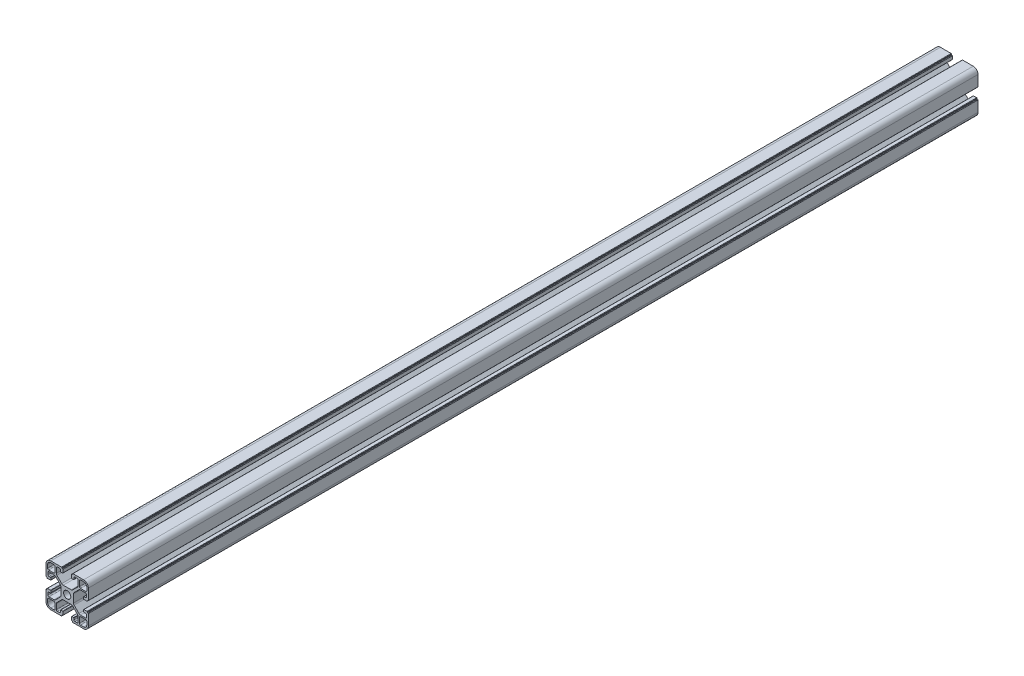
SolidWorks part; units mm, degrees
note: '?' marks a value the reader was unsure of.
material "6063-T5"
ref_plane "前视基准面" through (0, 0, 0) normal (0, 0, 1) x (1, 0, 0)
ref_plane "上视基准面" through (0, 0, 0) normal (0, 1, 0) x (1, 0, 0)
ref_plane "右视基准面" through (0, 0, 0) normal (1, 0, 0) x (0, 0, -1)
sketch "草图1" plane through (0, 0, 0) normal (0, 0, 1) x (1, 0, 0)
  line L0 (5.1, -19.2) -> (5.1, -19.7)
  line L1 (4.4, -19) -> (4.9, -19)
  line L2 (5.4, -20) -> (15.5, -20)
  line L3 (4.1, -15.8) -> (4.1, -18.8)
  line L4 (20, -15.5) -> (20, -5.4)
  line L5 (6.1, -15.5) -> (4.4, -15.5)
  line L6 (19.7, -5.1) -> (19.2, -5.1)
  line L7 (6.4, -17.2) -> (6.4, -15.8)
  line L8 (19, -4.9) -> (19, -4.4)
  line L9 (9.25, -18.2) -> (7.4, -18.2)
  line L10 (18.7, -4.1) -> (15.8, -4.1)
  line L11 (10.25, -12.4926) -> (10.25, -17.2)
  line L12 (15.5, -4.4) -> (15.5, -6.1)
  line L13 (5.1716, -6.5858) -> (9.6642, -11.0784)
  line L14 (15.8, -6.4) -> (17.2, -6.4)
  line L15 (-3.7574, -6) -> (3.7574, -6)
  line L16 (18.2, -7.4) -> (18.2, -9.25)
  line L17 (-9.6642, -11.0784) -> (-5.1716, -6.5858)
  line L18 (17.2, -10.25) -> (12.4926, -10.25)
  line L19 (-10.25, -17.2) -> (-10.25, -12.4926)
  line L20 (11.0784, -9.6642) -> (6.5858, -5.1716)
  line L21 (-7.4, -18.2) -> (-9.25, -18.2)
  line L22 (6, -3.7574) -> (6, 3.7574)
  line L23 (-6.4, -15.8) -> (-6.4, -17.2)
  line L24 (6.5858, 5.1716) -> (11.0784, 9.6642)
  line L25 (-4.4, -15.5) -> (-6.1, -15.5)
  line L26 (12.4926, 10.25) -> (17.2, 10.25)
  line L27 (-4.1, -18.8) -> (-4.1, -15.8)
  line L28 (18.2, 9.25) -> (18.2, 7.4)
  line L29 (-4.9, -19) -> (-4.4, -19)
  line L30 (17.2, 6.4) -> (15.8, 6.4)
  line L31 (-5.1, -19.7) -> (-5.1, -19.2)
  line L32 (15.5, 6.1) -> (15.5, 4.4)
  line L33 (-15.5, -20) -> (-5.4, -20)
  line L34 (15.8, 4.1) -> (18.7, 4.1)
  line L35 (-20, -5.4) -> (-20, -15.5)
  line L36 (19, 4.4) -> (19, 4.9)
  line L37 (-19.2, -5.1) -> (-19.7, -5.1)
  line L38 (19.2, 5.1) -> (19.7, 5.1)
  line L39 (-19, -4.4) -> (-19, -4.9)
  line L40 (20, 5.4) -> (20, 15.5)
  line L41 (-15.8, -4.1) -> (-18.7, -4.1)
  line L42 (15.5, 20) -> (5.4, 20)
  line L43 (-15.5, -6.1) -> (-15.5, -4.4)
  line L44 (5.1, 19.7) -> (5.1, 19.2)
  line L45 (-17.2, -6.4) -> (-15.8, -6.4)
  line L46 (4.9, 19) -> (4.4, 19)
  line L47 (-18.2, -9.25) -> (-18.2, -7.4)
  line L48 (4.1, 18.7) -> (4.1, 15.8)
  line L49 (-12.4926, -10.25) -> (-17.2, -10.25)
  line L50 (4.4, 15.5) -> (6.1, 15.5)
  line L51 (-6.5858, -5.1716) -> (-11.0784, -9.6642)
  line L52 (6.4, 15.8) -> (6.4, 17.2)
  line L53 (-6, 3.7574) -> (-6, -3.7574)
  line L54 (7.4, 18.2) -> (9.25, 18.2)
  line L55 (-11.0784, 9.6642) -> (-6.5858, 5.1716)
  line L56 (10.25, 17.2) -> (10.25, 12.4926)
  line L57 (-17.2, 10.25) -> (-12.4926, 10.25)
  line L58 (9.6642, 11.0784) -> (5.1716, 6.5858)
  line L59 (-18.2, 7.4) -> (-18.2, 9.25)
  line L60 (3.7574, 6) -> (-3.7574, 6)
  line L61 (-15.8, 6.4) -> (-17.2, 6.4)
  line L62 (-5.1716, 6.5858) -> (-9.6642, 11.0784)
  line L63 (-15.5, 4.4) -> (-15.5, 6.1)
  line L64 (-10.25, 12.4926) -> (-10.25, 17.2)
  line L65 (-18.7, 4.1) -> (-15.8, 4.1)
  line L66 (-9.25, 18.2) -> (-7.4, 18.2)
  line L67 (-19, 4.9) -> (-19, 4.4)
  line L68 (-6.4, 17.2) -> (-6.4, 15.8)
  line L69 (-19.7, 5.1) -> (-19.2, 5.1)
  line L70 (-6.1, 15.5) -> (-4.4, 15.5)
  line L71 (-20, 15.5) -> (-20, 5.4)
  line L72 (-4.1, 15.8) -> (-4.1, 18.7)
  line L73 (-5.4, 20) -> (-15.5, 20)
  line L74 (-4.4, 19) -> (-4.9, 19)
  line L75 (-5.1, 19.2) -> (-5.1, 19.7)
  line L76 (12.55, 18.5) -> (15.5, 18.5)
  line L77 (11.55, 12.55) -> (11.55, 17.5)
  line L78 (18.5, 15.5) -> (18.5, 12.55)
  line L79 (17.5, 11.55) -> (12.55, 11.55)
  line L80 (-11.55, 17.5) -> (-11.55, 12.55)
  line L81 (-15.5, 18.5) -> (-12.55, 18.5)
  line L82 (-12.55, 11.55) -> (-17.5, 11.55)
  line L83 (-18.5, 12.55) -> (-18.5, 15.5)
  line L84 (-12.55, -18.5) -> (-15.5, -18.5)
  line L85 (-11.55, -12.55) -> (-11.55, -17.5)
  line L86 (-18.5, -15.5) -> (-18.5, -12.55)
  line L87 (-17.5, -11.55) -> (-12.55, -11.55)
  line L88 (11.55, -17.5) -> (11.55, -12.55)
  line L89 (15.5, -18.5) -> (12.55, -18.5)
  line L90 (12.55, -11.55) -> (17.5, -11.55)
  line L91 (18.5, -12.55) -> (18.5, -15.5)
  arc A0 (5.1, -19.2) -> (4.9, -19) centre (4.9, -19.2) ccw
  arc A1 (5.1, -19.7) -> (5.4, -20) centre (5.4, -19.7) ccw
  arc A2 (4.1, -18.8) -> (4.4, -19) centre (4.3282, -18.7827) ccw
  arc A3 (15.5, -20) -> (20, -15.5) centre (15.5, -15.5) ccw
  arc A4 (4.4, -15.5) -> (4.1, -15.8) centre (4.4, -15.8) ccw
  arc A5 (20, -5.4) -> (19.7, -5.1) centre (19.7, -5.4) ccw
  arc A6 (6.4, -15.8) -> (6.1, -15.5) centre (6.1, -15.8) ccw
  arc A7 (19, -4.9) -> (19.2, -5.1) centre (19.2, -4.9) ccw
  arc A8 (6.4, -17.2) -> (7.4, -18.2) centre (7.4, -17.2) ccw
  arc A9 (19, -4.4) -> (18.7, -4.1) centre (18.7, -4.4) ccw
  arc A10 (9.25, -18.2) -> (10.25, -17.2) centre (9.25, -17.2) ccw
  arc A11 (15.8, -4.1) -> (15.5, -4.4) centre (15.8, -4.4) ccw
  arc A12 (10.25, -12.4926) -> (9.6642, -11.0784) centre (8.25, -12.4926) ccw
  arc A13 (15.5, -6.1) -> (15.8, -6.4) centre (15.8, -6.1) ccw
  arc A14 (5.1716, -6.5858) -> (3.7574, -6) centre (3.7574, -8) ccw
  arc A15 (18.2, -7.4) -> (17.2, -6.4) centre (17.2, -7.4) ccw
  arc A16 (-3.7574, -6) -> (-5.1716, -6.5858) centre (-3.7574, -8) ccw
  arc A17 (17.2, -10.25) -> (18.2, -9.25) centre (17.2, -9.25) ccw
  arc A18 (-9.6642, -11.0784) -> (-10.25, -12.4926) centre (-8.25, -12.4926) ccw
  arc A19 (11.0784, -9.6642) -> (12.4926, -10.25) centre (12.4926, -8.25) ccw
  arc A20 (-10.25, -17.2) -> (-9.25, -18.2) centre (-9.25, -17.2) ccw
  arc A21 (6, -3.7574) -> (6.5858, -5.1716) centre (8, -3.7574) ccw
  arc A22 (-7.4, -18.2) -> (-6.4, -17.2) centre (-7.4, -17.2) ccw
  arc A23 (6.5858, 5.1716) -> (6, 3.7574) centre (8, 3.7574) ccw
  arc A24 (-6.1, -15.5) -> (-6.4, -15.8) centre (-6.1, -15.8) ccw
  arc A25 (12.4926, 10.25) -> (11.0784, 9.6642) centre (12.4926, 8.25) ccw
  arc A26 (-4.1, -15.8) -> (-4.4, -15.5) centre (-4.4, -15.8) ccw
  arc A27 (18.2, 9.25) -> (17.2, 10.25) centre (17.2, 9.25) ccw
  arc A28 (-4.4, -19) -> (-4.1, -18.8) centre (-4.3282, -18.7827) ccw
  arc A29 (17.2, 6.4) -> (18.2, 7.4) centre (17.2, 7.4) ccw
  arc A30 (-4.9, -19) -> (-5.1, -19.2) centre (-4.9, -19.2) ccw
  arc A31 (15.8, 6.4) -> (15.5, 6.1) centre (15.8, 6.1) ccw
  arc A32 (-5.4, -20) -> (-5.1, -19.7) centre (-5.4, -19.7) ccw
  arc A33 (15.5, 4.4) -> (15.8, 4.1) centre (15.8, 4.4) ccw
  arc A34 (-20, -15.5) -> (-15.5, -20) centre (-15.5, -15.5) ccw
  arc A35 (18.7, 4.1) -> (19, 4.4) centre (18.7, 4.4) ccw
  arc A36 (-19.7, -5.1) -> (-20, -5.4) centre (-19.7, -5.4) ccw
  arc A37 (19.2, 5.1) -> (19, 4.9) centre (19.2, 4.9) ccw
  arc A38 (-19.2, -5.1) -> (-19, -4.9) centre (-19.2, -4.9) ccw
  arc A39 (19.7, 5.1) -> (20, 5.4) centre (19.7, 5.4) ccw
  arc A40 (-18.7, -4.1) -> (-19, -4.4) centre (-18.7, -4.4) ccw
  arc A41 (20, 15.5) -> (15.5, 20) centre (15.5, 15.5) ccw
  arc A42 (-15.5, -4.4) -> (-15.8, -4.1) centre (-15.8, -4.4) ccw
  arc A43 (5.4, 20) -> (5.1, 19.7) centre (5.4, 19.7) ccw
  arc A44 (-15.8, -6.4) -> (-15.5, -6.1) centre (-15.8, -6.1) ccw
  arc A45 (4.9, 19) -> (5.1, 19.2) centre (4.9, 19.2) ccw
  arc A46 (-17.2, -6.4) -> (-18.2, -7.4) centre (-17.2, -7.4) ccw
  arc A47 (4.4, 19) -> (4.1, 18.7) centre (4.4, 18.7) ccw
  arc A48 (-18.2, -9.25) -> (-17.2, -10.25) centre (-17.2, -9.25) ccw
  arc A49 (4.1, 15.8) -> (4.4, 15.5) centre (4.4, 15.8) ccw
  arc A50 (-12.4926, -10.25) -> (-11.0784, -9.6642) centre (-12.4926, -8.25) ccw
  arc A51 (6.1, 15.5) -> (6.4, 15.8) centre (6.1, 15.8) ccw
  arc A52 (-6.5858, -5.1716) -> (-6, -3.7574) centre (-8, -3.7574) ccw
  arc A53 (7.4, 18.2) -> (6.4, 17.2) centre (7.4, 17.2) ccw
  arc A54 (-6, 3.7574) -> (-6.5858, 5.1716) centre (-8, 3.7574) ccw
  arc A55 (10.25, 17.2) -> (9.25, 18.2) centre (9.25, 17.2) ccw
  arc A56 (-11.0784, 9.6642) -> (-12.4926, 10.25) centre (-12.4926, 8.25) ccw
  arc A57 (9.6642, 11.0784) -> (10.25, 12.4926) centre (8.25, 12.4926) ccw
  arc A58 (-17.2, 10.25) -> (-18.2, 9.25) centre (-17.2, 9.25) ccw
  arc A59 (3.7574, 6) -> (5.1716, 6.5858) centre (3.7574, 8) ccw
  arc A60 (-18.2, 7.4) -> (-17.2, 6.4) centre (-17.2, 7.4) ccw
  arc A61 (-5.1716, 6.5858) -> (-3.7574, 6) centre (-3.7574, 8) ccw
  arc A62 (-15.5, 6.1) -> (-15.8, 6.4) centre (-15.8, 6.1) ccw
  arc A63 (-10.25, 12.4926) -> (-9.6642, 11.0784) centre (-8.25, 12.4926) ccw
  arc A64 (-15.8, 4.1) -> (-15.5, 4.4) centre (-15.8, 4.4) ccw
  arc A65 (-9.25, 18.2) -> (-10.25, 17.2) centre (-9.25, 17.2) ccw
  arc A66 (-19, 4.4) -> (-18.7, 4.1) centre (-18.7, 4.4) ccw
  arc A67 (-6.4, 17.2) -> (-7.4, 18.2) centre (-7.4, 17.2) ccw
  arc A68 (-19, 4.9) -> (-19.2, 5.1) centre (-19.2, 4.9) ccw
  arc A69 (-6.4, 15.8) -> (-6.1, 15.5) centre (-6.1, 15.8) ccw
  arc A70 (-20, 5.4) -> (-19.7, 5.1) centre (-19.7, 5.4) ccw
  arc A71 (-4.4, 15.5) -> (-4.1, 15.8) centre (-4.4, 15.8) ccw
  arc A72 (-15.5, 20) -> (-20, 15.5) centre (-15.5, 15.5) ccw
  arc A73 (-4.1, 18.7) -> (-4.4, 19) centre (-4.4, 18.7) ccw
  arc A74 (-5.1, 19.7) -> (-5.4, 20) centre (-5.4, 19.7) ccw
  arc A75 (-5.1, 19.2) -> (-4.9, 19) centre (-4.9, 19.2) ccw
  arc A76 (12.55, 18.5) -> (11.55, 17.5) centre (12.55, 17.5) ccw
  arc A77 (18.5, 15.5) -> (15.5, 18.5) centre (15.5, 15.5) ccw
  arc A78 (11.55, 12.55) -> (12.55, 11.55) centre (12.55, 12.55) ccw
  arc A79 (17.5, 11.55) -> (18.5, 12.55) centre (17.5, 12.55) ccw
  arc A80 (-11.55, 17.5) -> (-12.55, 18.5) centre (-12.55, 17.5) ccw
  arc A81 (-12.55, 11.55) -> (-11.55, 12.55) centre (-12.55, 12.55) ccw
  arc A82 (-15.5, 18.5) -> (-18.5, 15.5) centre (-15.5, 15.5) ccw
  arc A83 (-18.5, 12.55) -> (-17.5, 11.55) centre (-17.5, 12.55) ccw
  circle A84 centre (0, 0) radius 3.4
  arc A85 (-12.55, -18.5) -> (-11.55, -17.5) centre (-12.55, -17.5) ccw
  arc A86 (-18.5, -15.5) -> (-15.5, -18.5) centre (-15.5, -15.5) ccw
  arc A87 (-11.55, -12.55) -> (-12.55, -11.55) centre (-12.55, -12.55) ccw
  arc A88 (-17.5, -11.55) -> (-18.5, -12.55) centre (-17.5, -12.55) ccw
  arc A89 (11.55, -17.5) -> (12.55, -18.5) centre (12.55, -17.5) ccw
  arc A90 (12.55, -11.55) -> (11.55, -12.55) centre (12.55, -12.55) ccw
  arc A91 (15.5, -18.5) -> (18.5, -15.5) centre (15.5, -15.5) ccw
  arc A92 (18.5, -12.55) -> (17.5, -11.55) centre (17.5, -12.55) ccw
extrude "凸台-拉伸1" add sketch "草图1" along normal blind 840
ref_axis "基准轴" through (0, 0, 0) along (0, 0, 1)?
ref_plane "基准面" through (0, 0, 20) normal (0, 0, -1) x (-1, 0, 0)
hole_wizard "螺纹孔E" [suppressed] positions "草图3" profile "草图2" tap size "M8" standard "GB"
sketch "草图3" plane through (0, 0, 300) normal (0, 0, 1) x (1, 0, 0)
  point P0 (0, 0)
sketch "草图2" plane through (0, 0, 300) normal (1, 0, 0) x (0, -1, 0)
  line L0 (0, 0) -> (0, 28.2959)
  line L1 (0, 28.2959) -> (3.405, 26.25)
  line L2 (3.405, 26.25) -> (3.405, 0)
  line L5 (3.405, 0) -> (0, 0)
  line L10 (0, 28.2959) -> (-3.405, 26.25) construction
  line L11 (0, -6.35) -> (0, 107.95) construction
  dimension "螺纹孔钻头直径" = 6.81
  dimension "螺纹孔钻头深度" = 26.25
  dimension "导头角度" = 118
cosmetic thread "孔螺蚊线1" [suppressed] parameters "D1"=20, "D2"=8
hole_wizard "螺纹孔S" [suppressed] positions "草图5" profile "草图4" tap size "M8" standard "GB"
sketch "草图5" plane through (0, 0, 0) normal (0, 0, -1) x (-1, 0, 0)
  point P0 (0, 0)
sketch "草图4" plane through (0, 0, 0) normal (1, 0, 0) x (0, 1, 0)
  line L0 (0, 0) -> (0, 28.2959)
  line L1 (0, 28.2959) -> (3.405, 26.25)
  line L2 (3.405, 26.25) -> (3.405, 0)
  line L5 (3.405, 0) -> (0, 0)
  line L10 (0, 28.2959) -> (-3.405, 26.25) construction
  line L11 (0, -6.35) -> (0, 107.95) construction
  dimension "螺纹孔钻头直径" = 6.81
  dimension "螺纹孔钻头深度" = 26.25
  dimension "导头角度" = 118
cosmetic thread "孔螺蚊线2" [suppressed] parameters "D1"=20, "D2"=8
other "内孔SA1" [suppressed] parameters "D1"=16.8
sketch "草图6" plane through (0, 20, 0) normal (0, 1, 0) x (1, 0, 0)
  line L0 (-5.4, 0) -> (-15.5, 0) construction
  line L1 (0, -22) -> (0, 22) construction
  circle A0 centre (0, -19) radius 10
  dimension "D1" = 20
  dimension "D2" = 19
other "内孔EA1" [suppressed] parameters "D1"=16.8
sketch "草图7" plane through (0, 20, 0) normal (0, 1, 0) x (1, 0, 0)
  line L0 (-5.4, -300) -> (-15.5, -300) construction
  line L1 (0, -22) -> (0, 22) construction
  circle A0 centre (0, -281) radius 10
  dimension "D1" = 20
  dimension "D2" = 19
other "内孔SB1" [suppressed] parameters "D1"=16.8
sketch "草图8" plane through (-20, 0, 0) normal (-1, 0, 0) x (0, 0, 1)
  line L0 (0, -5.4) -> (0, -15.5) construction
  line L1 (22, 0) -> (-22, 0) construction
  circle A0 centre (19, 0) radius 10
  dimension "D1" = 20
  dimension "D2" = 19
other "内孔EB1" [suppressed] parameters "D1"=16.8
sketch "草图9" plane through (-20, 0, 0) normal (-1, 0, 0) x (0, 0, 1)
  line L0 (300, -5.4) -> (300, -15.5) construction
  line L1 (22, 0) -> (-22, 0) construction
  circle A0 centre (281, 0) radius 10
  dimension "D1" = 20
  dimension "D2" = 19
other "内孔SC1" [suppressed] parameters "D1"=16.8
sketch "草图10" plane through (0, -20, 0) normal (0, -1, 0) x (-1, 0, 0)
  line L0 (-5.4, 0) -> (-15.5, 0) construction
  line L1 (0, 22) -> (0, -22) construction
  circle A0 centre (0, -19) radius 10
  dimension "D1" = 20
  dimension "D2" = 19
other "内孔EC1" [suppressed] parameters "D1"=16.8
sketch "草图11" plane through (0, -20, 0) normal (0, -1, 0) x (-1, 0, 0)
  line L0 (-5.4, -300) -> (-15.5, -300) construction
  line L1 (0, 22) -> (0, -22) construction
  circle A0 centre (0, -281) radius 10
  dimension "D1" = 20
  dimension "D2" = 19
other "内孔SD1" [suppressed] parameters "D1"=16.8
sketch "草图12" plane through (20, 0, 0) normal (1, 0, 0) x (0, 0, -1)
  line L0 (0, 5.4) -> (0, 15.5) construction
  line L1 (22, 0) -> (-22, 0) construction
  circle A0 centre (-19, 0) radius 10
  dimension "D1" = 20
  dimension "D2" = 19
other "内孔ED1" [suppressed] parameters "D1"=16.8
sketch "草图13" plane through (20, 0, 0) normal (1, 0, 0) x (0, 0, -1)
  line L0 (-300, 5.4) -> (-300, 15.5) construction
  line L1 (22, 0) -> (-22, 0) construction
  circle A0 centre (-281, 0) radius 10
  dimension "D1" = 20
  dimension "D2" = 19
other "锚孔SA1" [suppressed] parameters "D1"=40
sketch "草图14" plane through (0, 20, 0) normal (0, 1, 0) x (1, 0, 0)
  line L0 (-5.4, 0) -> (-15.5, 0) construction
  line L1 (0, -22) -> (0, 22) construction
  circle A0 centre (0, -18) radius 5.5
  dimension "D1" = 11
  dimension "D2" = 18
other "锚孔EA1" [suppressed] parameters "D1"=40
sketch "草图15" plane through (0, 20, 0) normal (0, 1, 0) x (1, 0, 0)
  line L0 (-5.4, -300) -> (-15.5, -300) construction
  line L1 (0, -22) -> (0, 22) construction
  circle A0 centre (0, -282) radius 5.5
  dimension "D1" = 11
  dimension "D2" = 18
other "锚孔SB1" [suppressed] parameters "D1"=40
sketch "草图16" plane through (-20, 0, 0) normal (-1, 0, 0) x (0, 0, 1)
  line L0 (0, -5.4) -> (0, -15.5) construction
  line L1 (22, 0) -> (-22, 0) construction
  circle A0 centre (18, 0) radius 5.5
  dimension "D1" = 11
  dimension "D2" = 18
other "锚孔EB1" [suppressed] parameters "D1"=40
sketch "草图17" plane through (-20, 0, 0) normal (-1, 0, 0) x (0, 0, 1)
  line L0 (300, -5.4) -> (300, -15.5) construction
  line L1 (22, 0) -> (-22, 0) construction
  circle A0 centre (282, 0) radius 5.5
  dimension "D1" = 11
  dimension "D2" = 18
other "锚孔SC1" [suppressed] parameters "D1"=40.1
sketch "草图18" plane through (0, -20, 0) normal (0, -1, 0) x (-1, 0, 0)
  line L0 (-5.4, 0) -> (-15.5, 0) construction
  line L1 (0, 22) -> (0, -22) construction
  circle A0 centre (0, -18) radius 5.5
  dimension "D1" = 11
  dimension "D2" = 18
other "锚孔EC1" [suppressed] parameters "D1"=40.1
sketch "草图19" plane through (0, -20, 0) normal (0, -1, 0) x (-1, 0, 0)
  line L0 (-5.4, -300) -> (-15.5, -300) construction
  line L1 (0, 22) -> (0, -22) construction
  circle A0 centre (0, -282) radius 5.5
  dimension "D1" = 11
  dimension "D2" = 18
other "锚孔SD1" [suppressed] parameters "D1"=40.1
sketch "草图20" plane through (20, 0, 0) normal (1, 0, 0) x (0, 0, -1)
  line L0 (0, 5.4) -> (0, 15.5) construction
  line L1 (22, 0) -> (-22, 0) construction
  circle A0 centre (-18, 0) radius 5.5
  dimension "D1" = 11
  dimension "D2" = 18
other "锚孔ED1" [suppressed] parameters "D1"=40.1
sketch "草图21" plane through (20, 0, 0) normal (1, 0, 0) x (0, 0, -1)
  line L0 (-300, 5.4) -> (-300, 15.5) construction
  line L1 (22, 0) -> (-22, 0) construction
  circle A0 centre (-282, 0) radius 5.5
  dimension "D1" = 11
  dimension "D2" = 18
